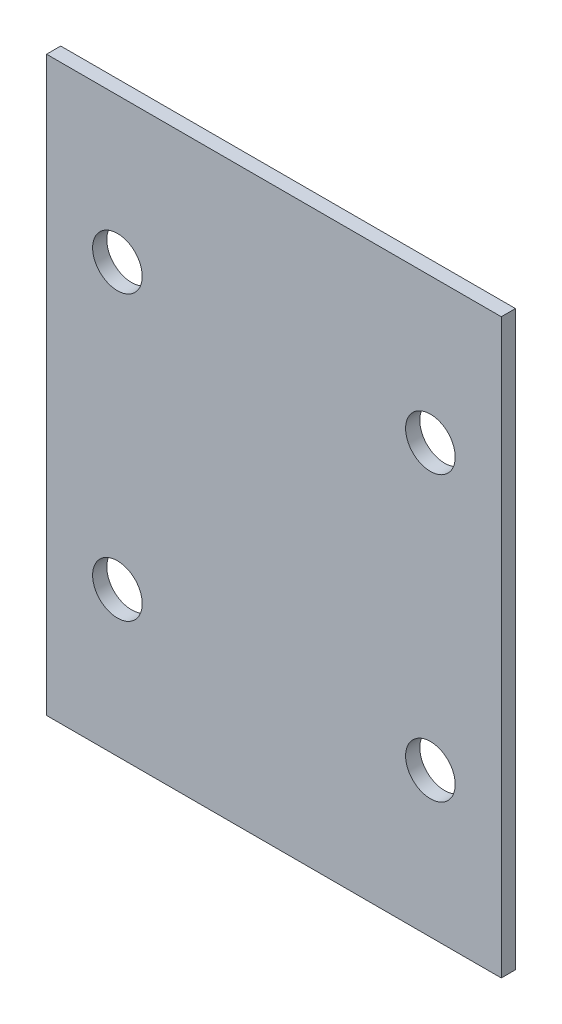
SolidWorks part; units mm, degrees
ref_plane "Front Plane" through (0, 0, 0) normal (0, 0, 1) x (1, 0, 0)
ref_plane "Top Plane" through (0, 0, 0) normal (0, 1, 0) x (1, 0, 0)
ref_plane "Right Plane" through (0, 0, 0) normal (1, 0, 0) x (0, 0, -1)
sketch "Sketch1" plane through (0, 0, 0) normal (0, 0, 1) x (1, 0, 0)
  line L1 (-20.2074, 267.3636) -> (183.5006, 267.3636)
  line L2 (-20.2074, 267.3636) -> (-20.2074, 10.8236)
  line L3 (-20.2074, 10.8236) -> (183.5006, 10.8236)
  line L4 (183.5006, 267.3636) -> (183.5006, 10.8236)
extrude "Boss-Extrude1" add sketch "Sketch1" along normal blind 6.35
sketch "Sketch2" plane through (0, 0, 0) normal (0, 0, -1) x (-1, 0, 0)
  line L0 (-151.7506, 202.5936) -> (-11.5426, 202.5936) construction
  line L1 (-11.5426, 202.5936) -> (-11.5426, 75.5936) construction
  line L2 (-11.5426, 75.5936) -> (-151.7506, 75.5936) construction
  line L3 (-151.7506, 75.5936) -> (-151.7506, 202.5936) construction
  line L4 (-183.5006, 139.0936) -> (20.2074, 139.0936) construction
  line L5 (-183.5006, 10.8236) -> (-183.5006, 267.3636) construction
  line L6 (20.2074, 267.3636) -> (20.2074, 10.8236) construction
  line L7 (-81.6466, 202.5936) -> (-81.6466, 75.5936) construction
  circle A0 centre (-151.7506, 202.5936) radius 11.1125
  circle A1 centre (-151.7506, 75.5936) radius 11.1125
  circle A2 centre (-11.5426, 202.5936) radius 11.1125
  circle A3 centre (-11.5426, 75.5936) radius 11.1125
  point P14 (-81.6466, 139.0936)
  dimension "D1" = 22.225
  dimension "D2" = 31.75
  dimension "D3" = 127
extrude "Cut-Extrude1" cut sketch "Sketch2" against normal up to next
